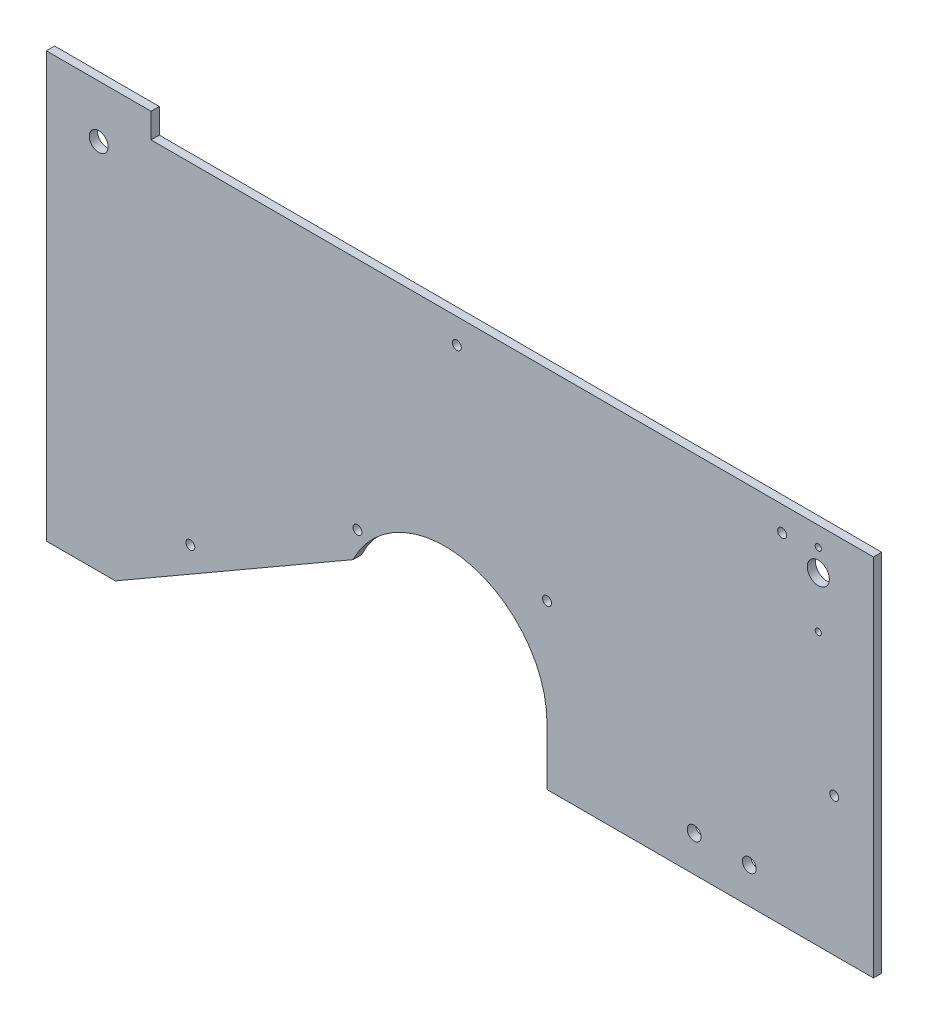
SolidWorks part; units mm, degrees
ref_plane "Front Plane" through (0, 0, 0) normal (0, 0, 1) x (1, 0, 0)
ref_plane "Top Plane" through (0, 0, 0) normal (0, 1, 0) x (1, 0, 0)
ref_plane "Right Plane" through (0, 0, 0) normal (1, 0, 0) x (0, 0, -1)
sketch "Sketch2" plane through (0, 0, 0) normal (0, 0, 1) x (1, 0, 0)
  line L0 (25.0304, 0) -> (111.2865, 49.8)
  line L1 (0, 0) -> (25.0304, 0)
  line L2 (0, 0) -> (0, 154)
  line L4 (300, 0) -> (300, 145)
  line L5 (181.6, 33.7) -> (181.6, 0)
  line L6 (181.6, 0) -> (300, 0)
  line L7 (19, 135) -> (19, 164.3674) construction
  line L11 (38, 145) -> (300, 145)
  line L12 (0, 154) -> (19, 154)
  line L13 (19, 154) -> (38, 154)
  line L14 (38, 154) -> (38, 145)
  line L15 (19, 135) -> (50019, 135) construction
  line L20 (19, 135) -> (19, -49865) construction
  circle A0 centre (19, 135) radius 3.425
  arc A1 (181.6, 33.7) -> (111.2865, 49.8) centre (144.6, 33.7) ccw
  point P19 (19, 154)
  dimension "D3" = 135
  dimension "D4" = 19
  dimension "D5" = 6.85
  dimension "D6" = 74
  dimension "D7" = 155.4
  dimension "D8" = 33.7
  dimension "D1" = 300
  dimension "D2" = 154
  dimension "D9" = 30
  dimension "D10" = 99.6
  dimension "D11" = 19
extrude "Boss-Extrude2" add sketch "Sketch2" along normal blind 3
sketch "Sketch3" plane through (0, 0, 3) normal (0, 0, 1) x (1, 0, 0)
  line L0 (300, 0) -> (300, 145) construction
  line L1 (181.6, 0) -> (300, 0)
  line L2 (181.6, 0) -> (181.6, 12.75)
  line L3 (181.6, 12.75) -> (300, 12.75)
  line L4 (300, 0) -> (300, 12.75)
  dimension "D1" = 12.75
extrude "Cut-Extrude1" cut sketch "Sketch3" against normal through all
sketch "Sketch4" plane through (0, 0, 3) normal (0, 0, 1) x (1, 0, 0)
  line L0 (19, 135) -> (19, -49865) construction
  line L1 (19, 135) -> (-49981, 135) construction
sketch "Sketch5" plane through (0, 0, 3) normal (0, 0, 1) x (1, 0, 0)
  line L0 (300, 12.75) -> (300, 145) construction
  line L1 (300, 12.75) -> (181.6, 12.75) construction
  line L2 (300, 145) -> (38, 145) construction
  line L3 (0, 154) -> (0, 0) construction
  line L4 (0, 0) -> (25.0304, 0) construction
  circle A0 centre (254.98, 25.75) radius 2.5
  circle A1 centre (234.98, 25.75) radius 2.5
  circle A2 centre (280, 130) radius 4
  circle A3 centre (280, 138) radius 1.125
  circle A4 centre (280, 111.5) radius 1.125
  circle A5 centre (181.6, 72.03) radius 1.625
  circle A6 centre (285.78, 62.92) radius 1.625
  circle A7 centre (52.23, 24.91) radius 1.625
  circle A8 centre (112.84, 59.93) radius 1.625
  circle A9 centre (266.89, 135.99) radius 1.625
  circle A10 centre (148.89, 135.99) radius 1.625
  dimension "D1" = 5
  dimension "D2" = 45.02
  dimension "D3" = 13
  dimension "D4" = 5
  dimension "D5" = 20
  dimension "D6" = 13
  dimension "D9" = 8
  dimension "D10" = 2.25
  dimension "D11" = 8
  dimension "D12" = 20
  dimension "D13" = 18.5
  dimension "D14" = 20
  dimension "D15" = 2.25
  dimension "D16" = 3.25
  dimension "D17" = 118.4
  dimension "D18" = 72.97
  dimension "D19" = 3.25
  dimension "D20" = 14.22
  dimension "D21" = 82.08
  dimension "D22" = 52.23
  dimension "D23" = 3.25
  dimension "D24" = 24.91
  dimension "D25" = 112.84
  dimension "D26" = 3.25
  dimension "D27" = 59.93
  dimension "D28" = 9.01
  dimension "D29" = 3.25
  dimension "D30" = 33.11
  dimension "D31" = 3.25
  dimension "D32" = 9.01
  dimension "D33" = 118
  dimension "D7" = 20
  dimension "D8" = 15
extrude "Cut-Extrude2" cut sketch "Sketch5" against normal through all
